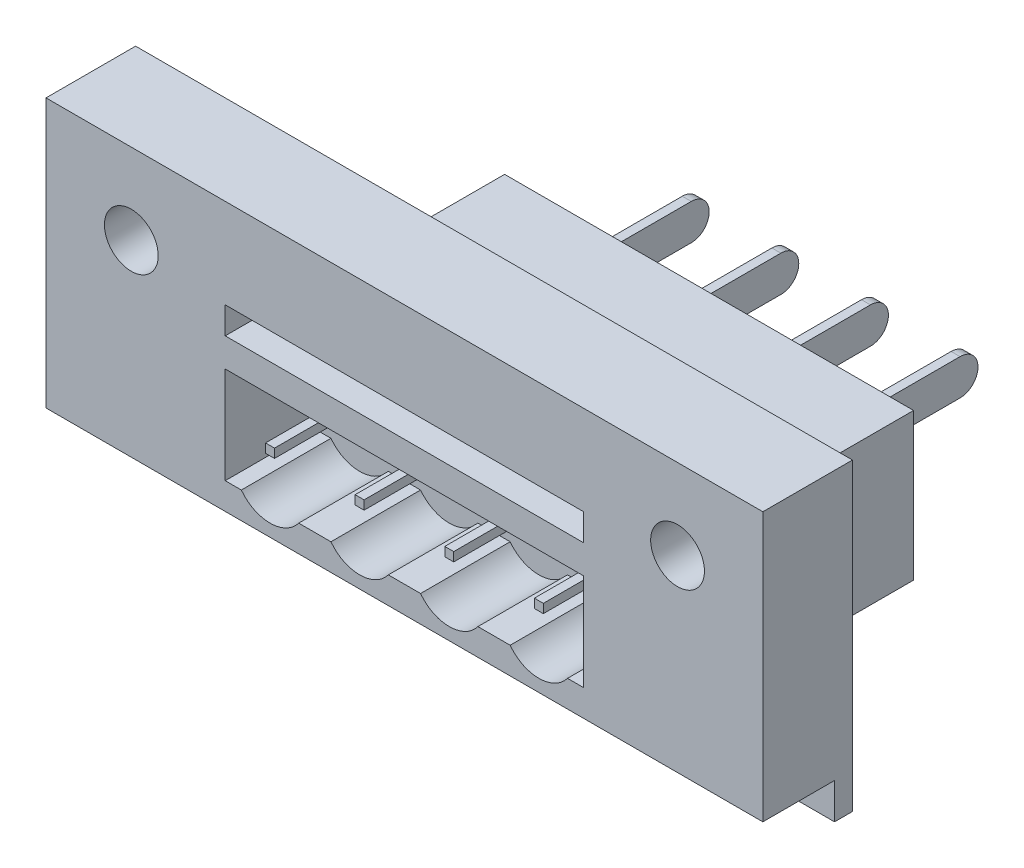
SolidWorks part; units mm, degrees
ref_plane "Front Plane" through (0, 0, 0) normal (0, 0, 1) x (1, 0, 0)
ref_plane "Top Plane" through (0, 0, 0) normal (0, 1, 0) x (1, 0, 0)
ref_plane "Right Plane" through (0, 0, 0) normal (1, 0, 0) x (0, 0, -1)
sketch "Sketch2" plane through (0, 0, 0) normal (0, 0, 1) x (1, 0, 0)
  line L0 (43.4756, 129.3243) -> (252.1422, 129.3243) construction
sketch "Sketch1" plane through (0, 0, 0) normal (0, 0, 1) x (1, 0, 0)
  line L0 (0, 7.493) -> (0, -7.493) construction
  line L1 (-20, 7.493) -> (20, 7.493)
  line L2 (-20, 7.493) -> (-20, -7.493)
  line L3 (-20, -7.493) -> (20, -7.493)
  line L4 (20, 7.493) -> (20, -7.493)
  line L5 (-20, 7.493) -> (20, -7.493) construction
  line L6 (-20, -7.493) -> (20, 7.493) construction
  line L7 (-11.41, -0.407) -> (11.41, -0.407)
  line L8 (-11.41, -0.407) -> (-11.41, -8.607)
  line L9 (-11.41, -8.607) -> (11.41, -8.607)
  line L10 (11.41, -8.607) -> (11.41, -0.407)
  line L11 (-15.24, 2.993) -> (15.24, 2.993) construction
  line L12 (-20, -7.493) -> (-20, -9.493)
  line L13 (-20, -9.493) -> (20, -9.493)
  line L14 (20, -9.493) -> (20, -7.493)
  line L15 (-5, -0.607) -> (-10, -0.607)
  line L16 (-10, 2.493) -> (10, 2.493)
  line L17 (-10, 2.493) -> (-10, 0.993)
  line L18 (-10, 0.993) -> (10, 0.993)
  line L19 (10, 2.493) -> (10, 0.993)
  line L20 (-10, -0.607) -> (-10, -6.007)
  line L21 (-10, -6.007) -> (-9.1, -6.007)
  line L22 (-5.9, -6.007) -> (-5, -6.007)
  line L23 (-5, -6.007) -> (-5, -0.607) construction
  line L24 (-12.5, -3.743) -> (12.5, -3.743) construction
  line L25 (-5, -0.607) -> (-5, -6.007)
  circle A0 centre (-15.24, 2.993) radius 1.5
  circle A1 centre (15.24, 2.993) radius 1.5
  arc A2 (-9.1, -6.007) -> (-5.9, -6.007) centre (-7.5, -4.807) ccw
  point P0 (0, 0)
  point P11 (0, -0.407)
  point P16 (0, 2.993)
  point P24 (0, 2.493)
  point P32 (-7.5, -6.807)
  point P37 (0, -3.743)
  dimension "D11" = 3
  dimension "D15" = 2
  dimension "D1" = 40
  dimension "D2" = 14.986
  dimension "D3" = 22.82
  dimension "D4" = 8.2
  dimension "D5" = 30.48
  dimension "D6" = 2
  dimension "D7" = 3.4
  dimension "D8" = 20
  dimension "D9" = 1.5
  dimension "D10" = 5
  dimension "D12" = 5
  dimension "D13" = 5.4
  dimension "D14" = 6.2
  dimension "D16" = 1.6
  dimension "D17" = 25
  dimension "D18" = 5.75
  dimension "D19" = 4.5
  dimension "D20" = 10
extrude "Boss-Extrude1" add sketch "Sketch1" along normal blind 5 contours L10 L3 L4 L1 L2 L8 L7 A1 A0 L16 L19 L18 L17 | L3 L10 L7 L8 A2 L21 L20 L15 L25 L22 | L21 A2 L22 L25 L15 L20 region at (0, 7.0658, 0) region at (1.6245, -4.0485, 0) region at (-7.5, -3.4951, 0)
extrude "Boss-Extrude2" add sketch "Sketch1<3>" along normal blind 1 contours L13 L14 L3 L10 L9 L8 L12 | L9 L10 L3 L8 region at (0, -8.6993, 0) region at (0, -8.05, 0)
sketch "Sketch1<3>" plane through (0, 0, 0) normal (0, 0, 1) x (1, 0, 0) same geometry as "Sketch1"
extrude "Cut-Extrude1" cut sketch "Sketch1<4>" along normal through all contours L21 A2 L22 L25 L15 L20 region at (-7.5, -3.4951, 0)
sketch "Sketch1<4>" plane through (0, 0, 0) normal (0, 0, 1) x (1, 0, 0) same geometry as "Sketch1"
pattern_linear "LPattern1" count 4 spacing 5 along (1, 0, 0) of "Cut-Extrude1"
extrude "Boss-Extrude3" add sketch "Sketch1<5>" against normal blind 12 contours L3 L10 L7 L8 A2 L21 L20 L15 L25 L22 | L21 A2 L22 L25 L15 L20 | L9 L10 L3 L8 region at (1.6245, -4.0485, 0) region at (0, -8.05, 0) region at (-7.5, -3.4951, 0)
sketch "Sketch1<5>" plane through (0, 0, 0) normal (0, 0, 1) x (1, 0, 0) same geometry as "Sketch1"
sketch "Sketch4" plane through (0, 0, 0) normal (0, 0, 1) x (1, 0, 0)
  line L1 (-7.75, -3.557) -> (-7.25, -3.557)
  line L2 (-7.75, -3.557) -> (-7.75, -3.057)
  line L3 (-7.75, -3.057) -> (-7.25, -3.057)
  line L4 (-7.25, -3.557) -> (-7.25, -3.057)
  line L5 (-7.75, -3.557) -> (-7.25, -3.057) construction
  line L6 (-7.75, -3.057) -> (-7.25, -3.557) construction
  line L8 (-10, -0.607) -> (-10, -6.007) construction
  point P0 (-7.5, -3.307)
  point P11 (-10, -3.307)
  dimension "D1" = 0.5
  dimension "D2" = 2.5
extrude "Boss-Extrude4" add sketch "Sketch4" along normal up to surface (5 mm away) up to face at (0, 0, 5)
sketch "Sketch5" plane through (0, 0, -12) normal (0, 0, -1) x (-1, 0, 0)
  line L0 (11.41, -0.407) -> (11.41, -8.607) construction
  line L1 (7.995, -3.507) -> (8.495, -3.507)
  line L2 (7.995, -3.507) -> (7.995, -5.507)
  line L3 (7.995, -5.507) -> (8.495, -5.507)
  line L4 (8.495, -3.507) -> (8.495, -5.507)
  line L5 (7.995, -3.507) -> (8.495, -5.507) construction
  line L6 (7.995, -5.507) -> (8.495, -3.507) construction
  line L7 (11.41, -8.607) -> (5.08, -8.607) construction
  point P0 (8.245, -4.507)
  point P5 (8.245, -8.607)
  point P13 (11.41, -4.507)
  dimension "D1" = 2
  dimension "D2" = 0.5
  dimension "D3" = 6.33
extrude "Boss-Extrude5" add sketch "Sketch5" along normal blind 8
fillet "Fillet1" radius 1 2 edges at (-8.245, -5.507, -20) (-8.245, -3.507, -20)
pattern_linear "LPattern2" count 4 spacing 5 along (1, 0, 0) of "Boss-Extrude4", "Boss-Extrude5", "Fillet1"
equation "\"P\"= 4'Number of pins"
equation "\"D1@Sketch1\"=\"P\"*5mm+20mm"
equation "\"D3@Sketch1\"=\"P\"*5.08mm+2.5mm"
equation "\"D5@Sketch1\"=(\"P\"-1)*5.08mm+15.24mm"
equation "\"D8@Sketch1\"=5mm*\"P\""
equation "\"D17@Sketch1\"=5mm*\"P\"+5mm"
equation "\"D1@LPattern1\"=\"P\""
equation "\"D1@LPattern2\"=\"P\""
